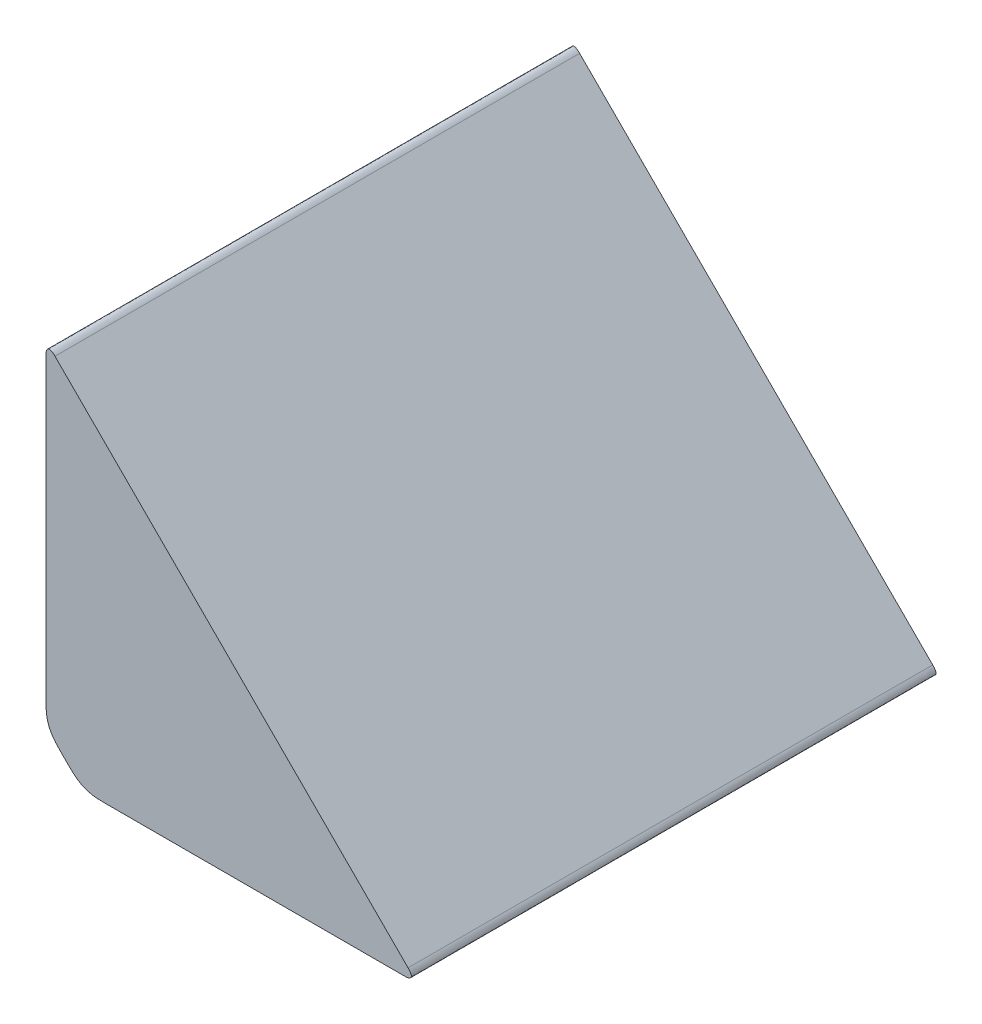
SolidWorks part; units mm, degrees
other "标注1"
sketch "草图2" plane through (-28.1439, 16.6017, 50.05) normal (-0.0832, 0.297, 0.9512) x (0.9955, -0.0191, 0.093)
ref_plane "Front Plane" through (0, 0, 0) normal (0, 0, 1) x (1, 0, 0)
ref_plane "Top Plane" through (0, 0, 0) normal (0, 1, 0) x (1, 0, 0)
ref_plane "Right Plane" through (0, 0, 0) normal (1, 0, 0) x (0, 0, -1)
sketch "草图1" plane through (0, 0, 0) normal (0, 0, 1) x (1, 0, 0)
  line L0 (-28.0939, -46.0291) -> (-28.0939, 17.6105)
  line L1 (-28.0939, 17.6105) -> (42.6168, -53.1002)
  line L2 (42.6168, -53.1002) -> (-21.0228, -53.1002)
  line L3 (-21.0228, -53.1002) -> (-28.0939, -46.0291)
  dimension "D1" = 100
  dimension "D2" = 10
extrude "凸台-拉伸1" add sketch "草图1" along normal mid plane 100
fillet "圆角1" radius 10 1 edges at (-28.0939, -46.0291, 0) curvature continuous yes
fillet "圆角2" radius 10 1 edges at (-21.0228, -53.1002, 0) curvature continuous yes
fillet "圆角3" radius 1 1 edges at (-28.0939, 17.6105, 0) curvature continuous yes
fillet "圆角4" radius 1 1 edges at (42.6168, -53.1002, 0) curvature continuous yes
